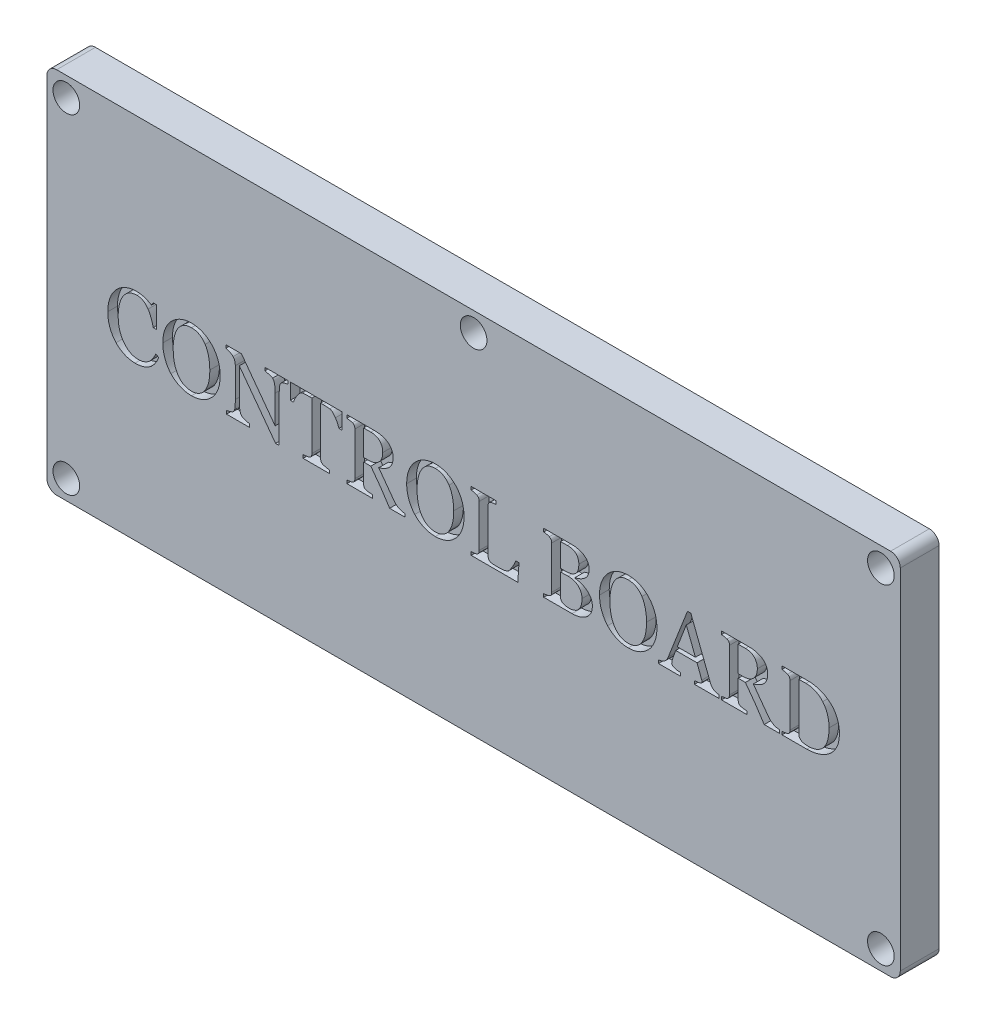
SolidWorks part; units mm, degrees
material "PLA Matte"
ref_plane "前视基准面" through (0, 0, 0) normal (0, 0, 1) x (1, 0, 0)
ref_plane "上视基准面" through (0, 0, 0) normal (0, 1, 0) x (1, 0, 0)
ref_plane "右视基准面" through (0, 0, 0) normal (1, 0, 0) x (0, 0, -1)
other "Configuration Table"
sketch "草图1" plane through (0, 0, 0) normal (0, 0, 1) x (1, 0, 0)
  line L1 (88, -38) -> (-88, -38)
  line L2 (88, -38) -> (88, 38)
  line L3 (88, 38) -> (-88, 38)
  line L4 (-88, -38) -> (-88, 38)
  line L5 (88, -38) -> (-88, 38) construction
  line L6 (88, 38) -> (-88, -38) construction
  point P0 (0, 0)
  dimension "D1" = 176
  dimension "D2" = 76
extrude "凸台-拉伸1" add sketch "草图1" along normal blind 8
sketch "草图2" plane through (0, 0, 0) normal (0, 0, -1) x (-1, 0, 0)
  line L0 (-88, -38) -> (-88, 38) construction
  line L1 (-88, 38) -> (88, 38) construction
  line L2 (88, -38) -> (-88, -38) construction
  line L3 (88, 38) -> (88, -38) construction
  circle A0 centre (-84, 34) radius 1.6
  circle A1 centre (-84, -34) radius 1.6
  circle A2 centre (-84, 0) radius 2.6
  circle A3 centre (0, 34) radius 1.6
  circle A4 centre (84, 34) radius 1.6
  circle A5 centre (84, 0) radius 2.6
  circle A6 centre (84, -34) radius 1.6
  circle A7 centre (0, -34) radius 2.6
  point P28 (0, 38)
  point P29 (-88, 0)
  dimension "D1" = 3.2
  dimension "D2" = 5.2
  dimension "D3" = 3.2
  dimension "D4" = 3.2
  dimension "D5" = 3.2
  dimension "D6" = 5.2
  dimension "D7" = 5.2
  dimension "D8" = 3.2
  dimension "D9" = 4
  dimension "D10" = 4
  dimension "D11" = 4
  dimension "D12" = 4
extrude "切除-拉伸1" cut sketch "草图2" against normal through all contours A0 | A3 | A4 | A1 | A6 region at (84, 34, 0) region at (0, 34, 0) region at (-84, 34, 0)
extrude "切除-拉伸2" cut sketch "草图2<3>" against normal blind 3 contours A2 | A7 | A5
sketch "草图2<3>" plane through (0, 0, 0) normal (0, 0, -1) x (-1, 0, 0) same geometry as "草图2"
sketch "草图4" plane through (0, 0, 8) normal (0, 0, 1) x (1, 0, 0)
  circle A0 centre (-84, 34) radius 2.75
  circle A1 centre (0, 34) radius 2.75
  circle A2 centre (-84, -34) radius 2.75
  circle A3 centre (84, 34) radius 2.75
  circle A4 centre (84, -34) radius 2.75
  dimension "D1" = 5.5
extrude "切除-拉伸3" cut sketch "草图4" against normal blind 4
fillet "圆角1" radius 2 4 edges at (88, 38, 4) (88, -38, 4) (-88, -38, 4) (-88, 38, 4)
sketch "草图5" plane through (0, 0, 8) normal (0, 0, 1) x (1, 0, 0)
  line L0 (-88, -6) -> (88, -6) construction
  line L1 (-88, 36) -> (-88, -36) construction
  line L2 (88, -36) -> (88, 36) construction
  line L3 (-86, -38) -> (86, -38) construction
  text T0 "CONTROL BOARD" font "Georgia" height in points 48
  dimension "D1" = 32
extrude "切除-拉伸4" cut sketch "草图5" against normal blind 2
